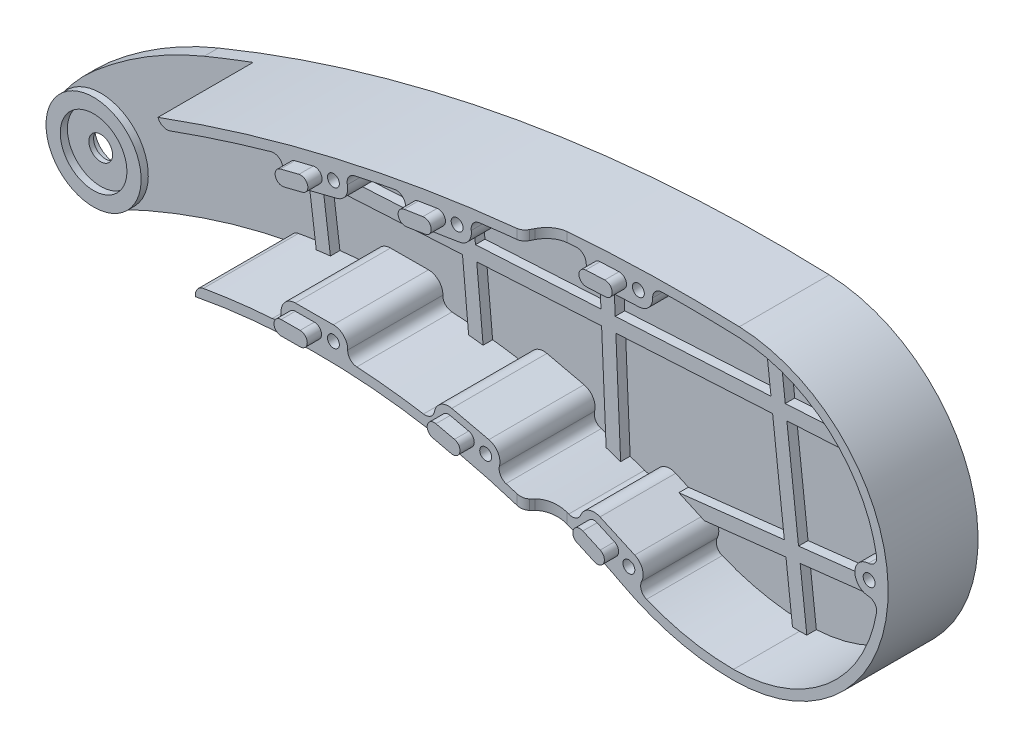
SolidWorks part; units mm, degrees
material "6061-T6 (SS)"
ref_plane "前视基准面" through (0, 0, 0) normal (0, 0, 1) x (1, 0, 0)
ref_plane "上视基准面" through (0, 0, 0) normal (0, 1, 0) x (1, 0, 0)
ref_plane "右视基准面" through (0, 0, 0) normal (1, 0, 0) x (0, 0, -1)
other "Configuration Table"
sketch "草图1" plane through (0, 0, 0) normal (0, 0, 1) x (1, 0, 0)
  line L0 (-74.3846, 0) -> (17.4339, 0) construction
  line L1 (0, 31.8895) -> (0, -25.7876) construction
  line L2 (0, 0) -> (19.2142, 13.9599) construction
  line L3 (0, 0) -> (13.9599, 19.2142) construction
  line L4 (0, 0) -> (-148.9161, -18) construction
  line L6 (0, 0) -> (-1.2281, 22.9672) construction
  line L8 (-1.2281, 22.9672) -> (-150.1441, 4.9672) construction
  line L9 (-150.1441, 4.9672) -> (-148.9161, -18) construction
  line L10 (-148.9161, -18) -> (-97.5528, -158.9319)
  line L12 (0, 0) -> (-103.1063, -167.9797) construction
  circle A117 centre (0, 0) radius 23.75 construction
  circle A118 centre (19.2142, 13.9599) radius 1.6
  circle A119 centre (13.9599, 19.2142) radius 1.6
  circle A120 centre (19.2142, -13.9599) radius 1.6
  circle A121 centre (13.9599, -19.2142) radius 1.6
  circle A122 centre (-13.9599, -19.2142) radius 1.6
  circle A123 centre (-19.2142, -13.9599) radius 1.6
  circle A124 centre (-19.2142, 13.9599) radius 1.6
  circle A125 centre (-13.9599, 19.2142) radius 1.6
  arc A126 (0, -32.5) -> (1.2171, 32.4772) centre (0, 0) ccw
  arc A127 (-157.1671, -12.3502) -> (-144.5702, -27.0063) centre (-148.9161, -18) ccw
  arc A134 (-28.3708, -24.2609) -> (-127.3793, -19.9637) centre (-83.3912, -149.2082) ccw
  arc A135 (-127.3793, -19.9637) -> (-144.5702, -27.0063) centre (-78.0965, -164.7651) ccw
  arc A136 (1.2171, 32.4772) -> (-127.1723, 9.5805) centre (-10.2849, -274.4361) ccw
  arc A138 (-23.6381, -26.5665) -> (-28.3708, -24.2609) centre (-55.9067, -86.7929) ccw
  arc A139 (0, -32.5) -> (-23.6381, -26.5665) centre (0, 17.5518) cw
  circle A153 centre (0, 0) radius 21.8
  arc A155 (-127.1723, 9.5805) -> (-150.1438, -4.5112) centre (-94.9478, -68.7195) ccw
  arc A156 (-150.1438, -4.5112) -> (-157.1671, -12.3502) centre (-123.7132, -35.2574) ccw
  point P27 (0, 0)
  point P73 (0, 0)
  point P83 (0, 0)
  point P105 (0, 0)
  dimension "D3" = 36
  dimension "D4" = 3.2
  dimension "D2" = 47.5
  dimension "D6" = 3.2
  dimension "D8" = 65
  dimension "D15" = 20
  dimension "D16" = 21.8
  dimension "D5" = 18
  dimension "D9" = 18
  dimension "D10" = 150
  dimension "D11" = 23
  dimension "D12" = 150
  dimension "D13" = 103.132
  dimension "D14" = 51.566
  dimension "D7" = 4
extrude "凸台-拉伸1" add sketch "草图1" along normal blind 3 contours A135 A134 A138 A126 A127 A125 A124 A123 A122 A121 A120 A119 A118 region at (-60.0806, 1.6127, 0)
sketch "草图2" plane through (0, 0, 0) normal (0, 0, -1) x (-1, 0, 0)
  line L0 (-28.5, 0) -> (0, 0) construction
  line L2 (0, 0) -> (-20.7479, 9.926) construction
  line L3 (-20.7479, 9.926) -> (128.1682, -8.074) construction
  line L4 (128.1682, -8.074) -> (148.9161, -18) construction
  line L5 (148.9161, -18) -> (265.6411, -112.2087) construction
  line L7 (-13.9568, 11.6234) -> (123.0533, -4.9375) construction
  line L9 (-14.5568, 6.6595) -> (122.4533, -9.9014) construction
  line L11 (19.8643, 25.54) -> (27.8561, 25.1781)
  line L13 (20.7667, -20.0677) -> (28.0595, -16.779)
  line L16 (53.5282, 22.5613) -> (61.4287, 21.3032)
  line L17 (79.2716, 17.6568) -> (87.0322, 15.7143)
  line L19 (80.013, -5.7241) -> (88.0129, -5.7588)
  line L20 (47.3274, -10.2892) -> (55.1237, -8.4956)
  line L21 (0, 0) -> (148.9161, -18) construction
  arc A111 (-1.1422, 30.4786) -> (-30.0624, 5.1483) centre (0, 0) ccw
  arc A112 (0, -30.5) -> (18.2871, -26.8842) centre (0, 17.5518) ccw
  arc A114 (75.0886, -10.9322) -> (61.0732, -12.4928) centre (83.3912, -149.2082) ccw
  arc A116 (144.5702, -27.0063) -> (157.1671, -12.3502) centre (148.9161, -18) ccw
  arc A118 (157.1671, -12.3502) -> (150.1438, -4.5112) centre (123.7132, -35.2574) ccw
  arc A119 (127.1723, 9.5805) -> (-1.2171, 32.4772) centre (10.2849, -274.4361) ccw
  arc A120 (-1.2171, 32.4772) -> (0, -32.5) centre (0, 0) ccw
  arc A121 (-1.0673, 28.48) -> (0, -28.5) centre (0, 0) ccw construction
  arc A122 (0, -32.5) -> (23.6381, -26.5665) centre (0, 17.5518) ccw
  arc A123 (28.3708, -24.2609) -> (23.6381, -26.5665) centre (55.9067, -86.7929) ccw
  arc A124 (127.3793, -19.9637) -> (28.3708, -24.2609) centre (83.3912, -149.2082) ccw
  arc A125 (144.5702, -27.0063) -> (127.3793, -19.9637) centre (78.0965, -164.7651) ccw
  arc A126 (144.5702, -27.0063) -> (157.1671, -12.3502) centre (148.9161, -18) ccw
  arc A128 (127.1723, 9.5805) -> (-1.2171, 32.4772) centre (10.2849, -274.4361) ccw
  arc A129 (-1.2171, 32.4772) -> (0, -32.5) centre (0, 0) ccw
  arc A130 (0, -32.5) -> (23.6381, -26.5665) centre (0, 17.5518) ccw
  arc A131 (28.3708, -24.2609) -> (23.6381, -26.5665) centre (55.9067, -86.7929) ccw
  arc A132 (127.3793, -19.9637) -> (28.3708, -24.2609) centre (83.3912, -149.2082) ccw
  arc A133 (144.5702, -27.0063) -> (127.3793, -19.9637) centre (78.0965, -164.7651) ccw
  arc A134 (0, -28.5) -> (21.749, -23.0407) centre (0, 17.5518) ccw construction
  arc A135 (26.7587, -20.6001) -> (21.749, -23.0407) centre (55.9067, -86.7929) ccw construction
  arc A136 (128.6681, -16.177) -> (26.7587, -20.6001) centre (83.3912, -149.2082) ccw construction
  arc A137 (146.3086, -23.4038) -> (128.6681, -16.177) centre (78.0965, -164.7651) ccw construction
  arc A138 (146.3086, -23.4038) -> (153.7238, -14.4104) centre (148.9161, -18) ccw construction
  arc A139 (153.7238, -14.4104) -> (126.0955, 5.6977) centre (120.8678, -30.5198) ccw construction
  arc A140 (126.0955, 5.6977) -> (-1.0673, 28.48) centre (10.2849, -274.4361) ccw construction
  arc A141 (-28.3421, -2.9958) -> (-28.3421, 2.9958) centre (-28.5, 0) ccw
  arc A142 (-28.3421, 2.9958) -> (-30.0624, 5.1483) centre (-28.2451, 4.837) cw
  arc A143 (-28.3421, -2.9958) -> (-30.0624, -5.1483) centre (-28.2451, -4.837) ccw
  arc A144 (-30.0624, -5.1483) -> (0, -30.5) centre (0, 0) ccw
  circle A145 centre (-28.5, 0) radius 1.6
  arc A146 (-1.1422, 30.4786) -> (0, -30.5) centre (0, 0) ccw construction
  circle A147 centre (-20.7479, 9.926) radius 7 construction
  circle A148 centre (128.1682, -8.074) radius 6 construction
  arc A149 (17.0011, 28.6182) -> (19.8643, 25.54) centre (20, 28.5369) ccw
  arc A150 (27.8561, 25.1781) -> (30.9858, 27.985) centre (27.9918, 28.175) ccw
  arc A151 (17.0011, 28.6182) -> (15.0491, 30.6555) centre (15.0181, 28.672) ccw
  arc A152 (30.9858, 27.985) -> (33.1139, 29.8374) centre (32.9655, 27.8593) cw
  arc A153 (15.0491, 30.6555) -> (-1.1422, 30.4786) centre (10.2849, -274.4361) ccw
  circle A154 centre (20, 28.5369) radius 1.6
  arc A155 (126.6313, 7.6402) -> (-1.1422, 30.4786) centre (10.2849, -274.4361) ccw construction
  arc A156 (19.3156, -24.1418) -> (20.7667, -20.0677) centre (22, -22.8025) cw
  arc A157 (28.0595, -16.779) -> (32.0817, -18.4083) centre (29.2928, -19.5138) cw
  circle A158 centre (22, -22.8025) radius 1.6
  arc A159 (19.3156, -24.1418) -> (18.2871, -26.8842) centre (17.5259, -25.0347) cw
  arc A160 (32.0817, -18.4083) -> (34.6447, -19.5434) centre (33.9409, -17.6713) ccw
  circle A161 centre (54, 25.524) radius 1.6
  arc A162 (27.5648, -22.4305) -> (22.6935, -24.8036) centre (55.9067, -86.7929) ccw construction
  arc A163 (0, -30.5) -> (22.6935, -24.8036) centre (0, 17.5518) ccw construction
  arc A164 (128.0237, -18.0703) -> (27.5648, -22.4305) centre (83.3912, -149.2082) ccw construction
  arc A165 (51.0293, 25.9419) -> (53.5282, 22.5613) centre (54, 25.524) ccw
  arc A166 (61.4287, 21.3032) -> (64.8541, 23.7404) centre (61.9005, 24.2659) ccw
  arc A167 (51.0293, 25.9419) -> (49.3187, 28.1856) centre (49.0649, 26.2183) ccw
  arc A168 (64.8541, 23.7404) -> (67.177, 25.3419) centre (66.8071, 23.393) cw
  arc A169 (49.3187, 28.1856) -> (33.1139, 29.8374) centre (10.2849, -274.4361) ccw
  circle A170 centre (80, 20.567) radius 1.6
  arc A171 (77.077, 21.2425) -> (79.2716, 17.6568) centre (80, 20.567) ccw
  arc A172 (87.0322, 15.7143) -> (90.6571, 17.8435) centre (87.7606, 18.6246) ccw
  arc A173 (77.077, 21.2425) -> (75.5687, 23.6269) centre (75.1443, 21.6892) ccw
  arc A175 (75.5687, 23.6269) -> (67.177, 25.3419) centre (10.2849, -274.4361) ccw
  circle A176 centre (48, -13.2128) radius 1.6
  circle A177 centre (80, -8.7241) radius 1.6
  arc A178 (45.1049, -13.9993) -> (47.3274, -10.2892) centre (48, -13.2128) cw
  arc A180 (45.1049, -13.9993) -> (43.7228, -16.4844) centre (43.1397, -14.5332) cw
  arc A182 (43.7228, -16.4844) -> (34.6447, -19.5434) centre (83.3912, -149.2082) ccw
  arc A183 (77.0018, -8.8285) -> (80.013, -5.7241) centre (80, -8.7241) cw
  arc A184 (88.0129, -5.7588) -> (90.9961, -8.9104) centre (87.9999, -8.7587) cw
  arc A185 (77.0018, -8.8285) -> (75.0886, -10.9322) centre (74.9666, -8.8993) cw
  arc A186 (90.9961, -8.9104) -> (92.8569, -11.0069) centre (92.9935, -9.0116) ccw
  arc A187 (107.3459, -12.77) -> (108.9673, -15.1002) centre (107, -14.7399) cw
  arc A188 (145.4394, -25.205) -> (128.0237, -18.0703) centre (78.0965, -164.7651) ccw construction
  arc A189 (128.0237, -18.0703) -> (27.5648, -22.4305) centre (83.3912, -149.2082) ccw
  arc A190 (145.4394, -25.205) -> (155.4422, -13.3729) centre (148.9161, -18) ccw construction
  arc A191 (75.5687, 23.6269) -> (93.1109, 19.2362) centre (10.2849, -274.4361) cw construction
  arc A192 (90.6571, 17.8435) -> (93.1109, 19.2362) centre (92.5724, 17.327) cw
  arc A193 (155.4422, -13.3729) -> (126.6313, 7.6402) centre (120.8678, -30.5198) ccw construction
  arc A194 (15.0491, 30.6555) -> (33.1139, 29.8374) centre (10.2849, -274.4361) cw construction
  arc A195 (49.3187, 28.1856) -> (67.177, 25.3419) centre (10.2849, -274.4361) cw construction
  arc A196 (93.1109, 19.2362) -> (114.3181, 12.4099) centre (10.2849, -274.4361) cw
  arc A197 (114.3181, 12.4099) -> (116.8779, 13.6021) centre (115, 14.2901) ccw
  arc A198 (55.1237, -8.4956) -> (58.7441, -10.8615) centre (55.7963, -11.4192) cw
  arc A199 (58.7441, -10.8615) -> (61.0732, -12.4928) centre (60.745, -10.4829) ccw
  arc A201 (27.5648, -22.4305) -> (22.6935, -24.8036) centre (55.9067, -86.7929) ccw
  arc A202 (0, -30.5) -> (22.6935, -24.8036) centre (0, 17.5518) ccw
  arc A203 (-1.1422, 30.4786) -> (0, -30.5) centre (0, 0) ccw
  arc A204 (126.4111, 7.731) -> (-1.1422, 30.4786) centre (10.2849, -274.4361) ccw
  arc A205 (148.8401, -6.0279) -> (126.4111, 7.731) centre (94.9478, -68.7195) ccw
  arc A206 (155.5169, -13.4802) -> (148.8401, -6.0279) centre (123.7132, -35.2574) ccw
  arc A207 (157.1671, -12.3502) -> (127.1723, 9.5805) centre (120.8678, -30.5198) ccw construction
  arc A208 (157.1671, -12.3502) -> (150.1438, -4.5112) centre (123.7132, -35.2574) ccw
  arc A209 (150.1438, -4.5112) -> (127.1723, 9.5805) centre (94.9478, -68.7195) ccw
  arc A210 (150.1438, -4.5112) -> (127.1723, 9.5805) centre (94.9478, -68.7195) ccw
  arc A211 (145.4394, -25.205) -> (155.5169, -13.4802) centre (148.9161, -18) ccw
  arc A212 (145.4394, -25.205) -> (128.0237, -18.0703) centre (78.0965, -164.7651) ccw
  point P113 (16.5105, -418.9921)
  arc M20 (127.1723, 9.5805) -> (-1.2171, 32.4772) centre (10.2849, -274.4361) ccw
  arc M21 (-1.2171, 32.4772) -> (0, -32.5) centre (0, 0) ccw
  arc M22 (0, -32.5) -> (23.6381, -26.5665) centre (0, 17.5518) ccw
  arc M23 (23.6381, -26.5665) -> (28.3708, -24.2609) centre (55.9067, -86.7929) cw
  arc M24 (28.3708, -24.2609) -> (127.3793, -19.9637) centre (83.3912, -149.2082) cw
  arc M25 (127.3793, -19.9637) -> (144.5702, -27.0063) centre (78.0965, -164.7651) cw
  dimension "D7" = 150
  dimension "D9" = 14
  dimension "D11" = 12
  dimension "D12" = 150
  dimension "D13" = 8
  dimension "D10" = 2.5
  dimension "D8" = 166.66
  dimension "D14" = 20
  dimension "D15" = 8
  dimension "D16" = 8
  dimension "D17" = 8
  dimension "D18" = 54
  dimension "D19" = 80
  dimension "D20" = 8
  dimension "D21" = 48
  dimension "D22" = 80
  dimension "D23" = 8
  dimension "D6" = 23
  dimension "D25" = 107
  dimension "D26" = 2
  dimension "D27" = 115
  dimension "D28" = 22
  dimension "D4" = 6
  dimension "D5" = 3.2
  dimension "D24" = 2
  dimension "D29" = 2
  dimension "D30" = 2
  dimension "D1" = 0
  dimension "D2" = 2
  dimension "D3" = 2
extrude "凸台-拉伸2" add sketch "草图2" along normal blind 20 contours M20 M21 M22 M23 M24 M25 | A152 A204 A151 A149 L11 A150 A154 | A168 A204 A167 A165 L16 A166 A161 | A192 A204 A173 A171 L17 A172 A170 | A189 A186 A184 L19 A183 A185 A177 | A199 A198 L20 A178 A180 A189 A176 | A159 A202 A201 A189 A160 A157 L13 A156 A158 | A142 A203 A143 A141 A145 region at (-24.5149, 27.9422, 0) region at (-6.9345, 32.3042, 0) region at (-58.4194, 24.4254, 0) region at (29.7748, 3.6145, 0) region at (-84.3067, 19.0872, 0) region at (-25.9289, -20.6304, 0) region at (-52.3362, -11.8146, 0) region at (-84.5374, -8.3524, 0)
sketch "草图4" plane through (0, 0, -20) normal (0, 0, -1) x (-1, 0, 0)
  line L0 (20, 28.5369) -> (27.9918, 28.175) construction
  line L3 (61.9005, 24.2659) -> (54, 25.524) construction
  line L8 (80, 20.567) -> (87.7606, 18.6246) construction
  line L9 (22, -22.8025) -> (29.2928, -19.5138) construction
  line L10 (48, -13.2128) -> (55.7963, -11.4192) construction
  line L11 (80, -8.7241) -> (87.9999, -8.7587) construction
  line L12 (29.2928, -19.5138) -> (25.6464, -21.1581) construction
  line L15 (29.9094, -20.8812) -> (26.263, -22.5255)
  line L24 (28.6761, -18.1464) -> (25.0297, -19.7907)
  line L27 (27.9918, 28.175) -> (23.9959, 28.356) construction
  line L30 (27.924, 26.6766) -> (23.9281, 26.8575)
  line L33 (28.0597, 29.6735) -> (24.0638, 29.8545)
  line L36 (61.9005, 24.2659) -> (57.9502, 24.8949) construction
  line L39 (87.7606, 18.6246) -> (83.8803, 19.5958) construction
  line L40 (87.3964, 17.1695) -> (83.5161, 18.1407)
  line L41 (88.1248, 20.0797) -> (84.2445, 21.0509)
  line L42 (87.9999, -8.7587) -> (84, -8.7414) construction
  line L43 (87.9934, -10.2587) -> (83.9935, -10.2414)
  line L44 (88.0064, -7.2587) -> (84.0065, -7.2414)
  line L45 (55.7963, -11.4192) -> (51.8982, -12.316) construction
  line L46 (56.1326, -12.881) -> (52.2345, -13.7778)
  line L47 (55.46, -9.9574) -> (51.5619, -10.8542)
  line L48 (61.6646, 22.7845) -> (57.7143, 23.4136)
  line L49 (62.1363, 25.7472) -> (58.1861, 26.3763)
  arc A24 (29.9094, -20.8812) -> (28.6761, -18.1464) centre (29.2928, -19.5138) ccw
  arc A25 (25.0297, -19.7907) -> (26.263, -22.5255) centre (25.6464, -21.1581) ccw
  arc A26 (27.924, 26.6766) -> (28.0597, 29.6735) centre (27.9918, 28.175) ccw
  arc A27 (24.0638, 29.8545) -> (23.9281, 26.8575) centre (23.9959, 28.356) ccw
  arc A30 (87.3964, 17.1695) -> (88.1248, 20.0797) centre (87.7606, 18.6246) ccw
  arc A31 (84.2445, 21.0509) -> (83.5161, 18.1407) centre (83.8803, 19.5958) ccw
  arc A32 (87.9934, -10.2587) -> (88.0064, -7.2587) centre (87.9999, -8.7587) ccw
  arc A33 (84.0065, -7.2414) -> (83.9935, -10.2414) centre (84, -8.7414) ccw
  arc A34 (56.1326, -12.881) -> (55.46, -9.9574) centre (55.7963, -11.4192) ccw
  arc A35 (51.5619, -10.8542) -> (52.2345, -13.7778) centre (51.8982, -12.316) ccw
  arc A36 (61.6646, 22.7845) -> (62.1363, 25.7472) centre (61.9005, 24.2659) ccw
  arc A37 (58.1861, 26.3763) -> (57.7143, 23.4136) centre (57.9502, 24.8949) ccw
  point P12 (27.4696, -20.3359)
  point P18 (25.9939, 28.2655)
  point P24 (59.9253, 24.5804)
  point P30 (85.8204, 19.1102)
  point P36 (85.9999, -8.7501)
  point P42 (53.8473, -11.8676)
  dimension "D2" = 1.5
  dimension "D1" = 4
extrude "凸台-拉伸3" add sketch "草图4" along normal blind 3 contours L44 A33 L43 A32 | L33 A27 L30 A26 | L49 A37 L48 A36 | A30 L41 A31 L40 | A34 L47 A35 L46 | A24 L24 A25 L15 region at (-85.9999, -8.7501, -20)
sketch "草图5" plane through (0, 0, -20) normal (0, 0, -1) x (-1, 0, 0)
  circle A0 centre (80, -8.7241) radius 1.6 construction
  circle A2 centre (-28.5, 0) radius 1.6 construction
  circle A4 centre (-28.5, 0) radius 1.6
  circle A6 centre (54, 25.524) radius 1.6 construction
  circle A8 centre (80, 20.567) radius 1.6 construction
  circle A10 centre (80, -8.7241) radius 1.6
  circle A12 centre (48, -13.2128) radius 1.6 construction
  circle A14 centre (22, -22.8025) radius 1.6 construction
  circle A27 centre (20, 28.5369) radius 1.6 construction
  circle A28 centre (54, 25.524) radius 1.6
  circle A29 centre (80, 20.567) radius 1.6
  circle A31 centre (48, -13.2128) radius 1.6
  circle A32 centre (22, -22.8025) radius 1.6
  circle A33 centre (20, 28.5369) radius 1.6
extrude "切除-拉伸1" cut sketch "草图5" against normal up to next
sketch "草图10" plane through (0, 0, 0) normal (0, 0, -1) x (-1, 0, 0)
  circle A0 centre (148.9161, -18) radius 2.5
  dimension "D1" = 5
extrude "切除-拉伸4" cut sketch "草图10" against normal up to next
sketch "草图11" plane through (0, 0, 3) normal (0, 0, 1) x (1, 0, 0)
  circle A0 centre (-148.9161, -18) radius 4.25
  dimension "D1" = 8.5
extrude "切除-拉伸5" cut sketch "草图11" against normal blind 2
sketch "草图13" plane through (0, 0, 3) normal (0, 0, 1) x (1, 0, 0)
  line L0 (-82.9126, 19.8482) -> (-83.8746, 23.7461)
  line L1 (-77.0737, 21.2281) -> (-77.9584, 25.1442)
  line L2 (-56.9642, 25.062) -> (-57.5825, 29.0289)
  line L3 (-51.0272, 25.9272) -> (-51.5669, 29.9056)
  line L4 (-22.9974, 28.4111) -> (-23.1657, 32.4224)
  line L5 (-17.0007, 28.6034) -> (-17.0897, 32.6173)
  line L6 (-83, -8.7157) -> (-83.011, -12.6837)
  line L7 (-77.0031, -8.8605) -> (-77.1835, -12.8243)
  line L10 (-24.5347, -21.1976) -> (-26.898, -24.9303)
  line L11 (-19.2779, -24.0635) -> (-21.0383, -27.8637)
  line L12 (28.5, 3) -> (32.3612, 3)
  line L13 (28.5, -3) -> (32.3612, -3)
  line L14 (28.5, 3) -> (28.5, -3) construction
  line L16 (-45.1135, -14.0301) -> (-46.1946, -17.848)
  line L17 (-50.9188, -12.5194) -> (-51.8359, -16.3799)
  arc A0 (-82.9126, 19.8482) -> (-77.0737, 21.2281) centre (-80, 20.567) ccw
  arc A1 (-56.9642, 25.062) -> (-51.0272, 25.9272) centre (-54, 25.524) ccw
  arc A2 (-22.9974, 28.4111) -> (-17.0007, 28.6034) centre (-20, 28.5369) ccw
  arc A3 (28.5, 3) -> (28.5, -3) centre (28.5, 0) ccw
  arc A5 (-45.1135, -14.0301) -> (-50.9676, -12.7729) centre (-48, -13.2128) ccw
  arc A7 (-23.6381, -26.5665) -> (0, -32.5) centre (0, 17.5518) ccw construction
  arc A8 (1.2171, 32.4772) -> (-127.1723, 9.5805) centre (-10.2849, -274.4361) ccw construction
  arc A9 (-28.3708, -24.2609) -> (-127.3793, -19.9637) centre (-83.3912, -149.2082) ccw construction
  arc A11 (-23.6381, -26.5665) -> (-28.3708, -24.2609) centre (-55.9067, -86.7929) ccw construction
  arc A12 (0, -32.5) -> (1.2171, 32.4772) centre (0, 0) ccw construction
  arc A13 (-17.0897, 32.6173) -> (-23.1657, 32.4224) centre (-10.2849, -274.4361) ccw
  arc A15 (32.3612, -3) -> (32.3612, 3) centre (0, 0) ccw
  arc A16 (-77.1835, -12.8243) -> (-83.011, -12.6837) centre (-83.3912, -149.2082) ccw
  arc A18 (-19.2779, -24.0635) -> (-24.5347, -21.1976) centre (-22, -22.8025) ccw
  arc A19 (-46.1946, -17.848) -> (-51.8359, -16.3799) centre (-83.3912, -149.2082) ccw
  arc A20 (-77.0031, -8.8605) -> (-83, -8.7157) centre (-80, -8.7241) ccw
  arc A21 (-77.9584, 25.1442) -> (-83.8746, 23.7461) centre (-10.2849, -274.4361) ccw
  arc A22 (-51.5669, 29.9056) -> (-57.5825, 29.0289) centre (-10.2849, -274.4361) ccw
  arc A23 (-23.6381, -26.5665) -> (-21.0383, -27.8637) centre (0, 17.5518) ccw
  arc A24 (-23.6381, -26.5665) -> (-26.898, -24.9303) centre (-55.9067, -86.7929) ccw
  circle M9 centre (28.5, 0) radius 1.6
  circle M10 centre (-54, 25.524) radius 1.6
  circle M11 centre (-80, 20.567) radius 1.6
  circle M12 centre (-80, -8.7241) radius 1.6
  circle M13 centre (-48, -13.2128) radius 1.6
  circle M14 centre (-22, -22.8025) radius 1.6
  circle M15 centre (-20, 28.5369) radius 1.6
  arc M17 (-127.3793, -19.9637) -> (-28.3708, -24.2609) centre (-83.3912, -149.2082) cw
  arc M19 (-23.6381, -26.5665) -> (0, -32.5) centre (0, 17.5518) ccw
  arc M20 (0, -32.5) -> (1.2171, 32.4772) centre (0, 0) ccw
  arc M21 (1.2171, 32.4772) -> (-127.1723, 9.5805) centre (-10.2849, -274.4361) ccw
  dimension "D1" = 6
  dimension "D2" = 6
  dimension "D3" = 3
  dimension "D4" = 6
  dimension "D5" = 0
extrude "切除-拉伸6" cut sketch "草图13" against normal blind 2 contours A5 M17 M13 | L11 A18 L10 M19 M14 | L12 L14 L13 M9 M20 | L14 A3 M9 | L4 A2 L5 M21 M15 | L2 A1 L3 M21 M10 | L0 A0 L1 M21 M11 | L7 A20 L6 M17 M12 region at (-22.2972, -27.133, 3) region at (30.7421, 0, 3) region at (-20.1252, 32.441, 3) region at (-54.5626, 29.3843, 3) region at (-83.2943, 21.8217, 3) region at (28.4329, 2.3, 3) region at (-79.9298, -5.8179, 3) region at (-51.2776, -14.4733, 3)
sketch "草图14" plane through (0, 0, 0) normal (0, 0, -1) x (-1, 0, 0)
  circle A0 centre (148.9161, -18) radius 10
  circle A1 centre (148.9161, -18) radius 7
  dimension "D1" = 14
  dimension "D2" = 20
extrude "凸台-拉伸4" add sketch "草图14" along normal blind 1.5
sketch "草图16" plane through (0, 0, 0) normal (0, 0, -1) x (-1, 0, 0)
  line L2 (69.9, 24.8123) -> (66.5383, -11.7121)
  line L3 (72.857, 24.208) -> (69.5822, -11.3731)
  line L4 (41.2273, 29.1197) -> (39.1573, -17.9354) construction
  line L5 (68.061, -11.534) -> (71.3789, 24.5139) construction
  line L6 (39.7324, 29.2684) -> (37.6328, -18.459)
  line L7 (42.7219, 28.9636) -> (40.6809, -17.4318)
  line L8 (103.7768, 16.0167) -> (100.1246, -11.6975) construction
  line L9 (102.3249, 16.48) -> (98.6344, -11.5244)
  line L10 (105.2277, 15.5457) -> (101.6126, -11.8868)
  arc A0 (69.5822, -11.3731) -> (66.5383, -11.7121) centre (83.3912, -149.2082) ccw
  arc A1 (72.857, 24.208) -> (69.9, 24.8123) centre (10.2849, -274.4361) ccw
  arc A2 (43.7228, -16.4844) -> (34.6447, -19.5434) centre (83.3912, -149.2082) ccw construction
  arc A5 (49.3187, 28.1856) -> (33.1139, 29.8374) centre (10.2849, -274.4361) ccw construction
  arc A8 (75.5687, 23.6269) -> (67.177, 25.3419) centre (10.2849, -274.4361) ccw construction
  arc A9 (75.0886, -10.9322) -> (61.0732, -12.4928) centre (83.3912, -149.2082) ccw construction
  arc A10 (75.0886, -10.9322) -> (61.0732, -12.4928) centre (83.3912, -149.2082) ccw construction
  arc A11 (49.3187, 28.1856) -> (33.1139, 29.8374) centre (10.2849, -274.4361) ccw construction
  arc A12 (43.7228, -16.4844) -> (34.6447, -19.5434) centre (83.3912, -149.2082) ccw construction
  arc A13 (40.6809, -17.4318) -> (37.6328, -18.459) centre (83.3912, -149.2082) ccw
  arc A14 (42.7219, 28.9636) -> (39.7324, 29.2684) centre (10.2849, -274.4361) ccw
  arc A15 (114.3181, 12.4099) -> (93.1109, 19.2362) centre (10.2849, -274.4361) ccw construction
  arc A16 (107.3459, -12.77) -> (92.8569, -11.0069) centre (83.3912, -149.2082) ccw construction
  arc A17 (101.6126, -11.8868) -> (98.6344, -11.5244) centre (83.3912, -149.2082) ccw
  arc A18 (105.2277, 15.5457) -> (102.3249, 16.48) centre (10.2849, -274.4361) ccw
  point P33 (71.3789, 24.5139)
  dimension "D3" = 3
  dimension "D1" = 3
  dimension "D2" = 3
extrude "凸台-拉伸5" add sketch "草图16" along normal blind 2
sketch "草图17" plane through (0, 0, 0) normal (0, 0, -1) x (-1, 0, 0)
  line L0 (41.7014, 5.7659) -> (100.4797, 2.4778) construction
  line L1 (40.6809, -17.4318) -> (42.7219, 28.9636) construction
  line L2 (102.3249, 16.48) -> (98.6344, -11.5244) construction
  line L3 (41.7673, 7.2646) -> (100.6762, 3.9692)
  line L4 (102.3249, 16.48) -> (98.6344, -11.5244) construction
  line L5 (41.6355, 4.2673) -> (100.2831, 0.9865)
  line L6 (100.6762, 3.9692) -> (100.2831, 0.9865)
  line L7 (41.6355, 4.2673) -> (41.7673, 7.2646)
  dimension "D1" = 3
extrude "凸台-拉伸6" add sketch "草图17" along normal blind 2
fillet "圆角1" radius 2 14 edges at (-83.8746, 23.7461, 2) (-77.9584, 25.1442, 2) (-57.5825, 29.0289, 2) (-51.5669, 29.9056, 2) (-77.1835, -12.8243, 2) (-83.011, -12.6837, 2) (-21.0383, -27.8637, 2) (32.3612, 3, 2) (32.3612, -3, 2) (-23.1657, 32.4224, 2) (-17.0897, 32.6173, 2) (-46.1946, -17.848, 2) (-51.8359, -16.3799, 2) (-26.898, -24.9303, 2)
sketch "草图20" plane through (0, 0, 3) normal (0, 0, 1) x (1, 0, 0)
  line L0 (30.0874, 3) -> (28.5, 3) construction
  line L1 (28.5, -3) -> (30.0874, -3) construction
  line L2 (-20.1802, -26.0112) -> (-19.2779, -24.0635) construction
  line L3 (-24.5347, -21.1976) -> (-25.967, -23.4599) construction
  line L4 (-45.6536, -15.9376) -> (-45.1135, -14.0301) construction
  line L5 (-50.9188, -12.5194) -> (-51.377, -14.4481) construction
  line L6 (-77.0932, -10.8408) -> (-77.0031, -8.8605) construction
  line L7 (-83, -8.7157) -> (-83.0055, -10.6981) construction
  line L8 (-23.0816, 30.4176) -> (-22.9974, 28.4111) construction
  line L9 (-17.0007, 28.6034) -> (-17.0452, 30.6112) construction
  line L10 (-57.2735, 27.0463) -> (-56.9642, 25.062) construction
  line L11 (-51.0272, 25.9272) -> (-51.2972, 27.9173) construction
  line L12 (-83.3938, 21.798) -> (-82.9126, 19.8482) construction
  line L13 (-77.0737, 21.2281) -> (-77.5162, 23.187) construction
  line L14 (30.0874, 3) -> (28.5, 3)
  line L15 (28.5, -3) -> (30.0874, -3)
  line L16 (-20.1802, -26.0112) -> (-19.2779, -24.0635)
  line L17 (-24.5347, -21.1976) -> (-25.967, -23.4599)
  line L18 (-45.6536, -15.9376) -> (-45.1135, -14.0301)
  line L19 (-50.9188, -12.5194) -> (-51.377, -14.4481)
  line L20 (-77.0932, -10.8408) -> (-77.0031, -8.8605)
  line L21 (-83, -8.7157) -> (-83.0055, -10.6981)
  line L22 (-23.0816, 30.4176) -> (-22.9974, 28.4111)
  line L23 (-17.0007, 28.6034) -> (-17.0452, 30.6112)
  line L24 (-57.2735, 27.0463) -> (-56.9642, 25.062)
  line L25 (-51.0272, 25.9272) -> (-51.2972, 27.9173)
  line L26 (-83.3938, 21.798) -> (-82.9126, 19.8482)
  line L27 (-77.0737, 21.2281) -> (-77.5162, 23.187)
  arc A0 (28.5, 3) -> (28.5, -3) centre (28.5, 0) ccw construction
  arc A1 (32.0603, -5.3279) -> (30.0874, -3) centre (30.0874, -5) ccw construction
  arc A2 (32.0603, -5.3279) -> (32.0603, 5.3279) centre (0, 0) ccw construction
  arc A3 (30.0874, 3) -> (32.0603, 5.3279) centre (30.0874, 5) ccw construction
  arc A4 (-19.2779, -24.0635) -> (-24.5347, -21.1976) centre (-22, -22.8025) ccw construction
  arc A5 (-28.4615, -24.221) -> (-25.967, -23.4599) centre (-27.6568, -22.39) ccw construction
  arc A7 (-23.6381, -26.5665) -> (-19.1298, -28.7) centre (0, 17.5518) ccw construction
  arc A8 (-20.1802, -26.0112) -> (-19.1298, -28.7) centre (-18.3654, -26.8519) ccw construction
  arc A9 (-45.1135, -14.0301) -> (-50.9188, -12.5194) centre (-48, -13.2128) ccw construction
  arc A10 (-53.7569, -15.9382) -> (-51.377, -14.4481) centre (-53.3228, -13.9859) ccw construction
  arc A11 (-44.3019, -18.3987) -> (-53.7569, -15.9382) centre (-83.3912, -149.2082) ccw construction
  arc A12 (-45.6536, -15.9376) -> (-44.3019, -18.3987) centre (-43.7293, -16.4825) ccw construction
  arc A13 (-77.0031, -8.8605) -> (-83, -8.7157) centre (-80, -8.7241) ccw construction
  arc A14 (-84.9822, -12.6924) -> (-83.0055, -10.6981) centre (-85.0055, -10.6925) ccw construction
  arc A15 (-75.2151, -12.9282) -> (-84.9822, -12.6924) centre (-83.3912, -149.2082) ccw construction
  arc A16 (-77.0932, -10.8408) -> (-75.2151, -12.9282) centre (-75.0953, -10.9318) ccw construction
  arc A17 (-22.9974, 28.4111) -> (-17.0007, 28.6034) centre (-20, 28.5369) ccw construction
  arc A18 (-15.0769, 32.6553) -> (-17.0452, 30.6112) centre (-15.0457, 30.6555) ccw construction
  arc A19 (-15.0769, 32.6553) -> (-25.1768, 32.3314) centre (-10.2849, -274.4361) ccw construction
  arc A20 (-23.0816, 30.4176) -> (-25.1768, 32.3314) centre (-25.0798, 30.3338) ccw construction
  arc A21 (-56.9642, 25.062) -> (-51.0272, 25.9272) centre (-54, 25.524) ccw construction
  arc A22 (-49.5711, 30.1696) -> (-51.2972, 27.9173) centre (-49.3153, 28.1861) ccw construction
  arc A23 (-49.5711, 30.1696) -> (-59.5706, 28.7124) centre (-10.2849, -274.4361) ccw construction
  arc A24 (-57.2735, 27.0463) -> (-59.5706, 28.7124) centre (-59.2496, 26.7383) ccw construction
  arc A25 (-82.9126, 19.8482) -> (-77.0737, 21.2281) centre (-80, 20.567) ccw construction
  arc A26 (-75.9933, 25.5814) -> (-77.5162, 23.187) centre (-75.5654, 23.6277) ccw construction
  arc A27 (-75.9933, 25.5814) -> (-85.8275, 23.2574) centre (-10.2849, -274.4361) ccw construction
  arc A28 (-83.3938, 21.798) -> (-85.8275, 23.2574) centre (-85.3355, 21.3188) ccw construction
  arc A29 (28.5, 3) -> (28.5, -3) centre (28.5, 0) ccw
  arc A30 (32.0603, -5.3279) -> (30.0874, -3) centre (30.0874, -5) ccw
  arc A31 (32.0603, -5.3279) -> (32.0603, 5.3279) centre (0, 0) ccw
  arc A32 (30.0874, 3) -> (32.0603, 5.3279) centre (30.0874, 5) ccw
  arc A33 (-19.2779, -24.0635) -> (-24.5347, -21.1976) centre (-22, -22.8025) ccw
  arc A34 (-28.4615, -24.221) -> (-25.967, -23.4599) centre (-27.6568, -22.39) ccw
  arc A35 (-23.6381, -26.5665) -> (-28.4615, -24.221) centre (-55.9071, -86.7927) ccw
  arc A36 (-23.6381, -26.5665) -> (-19.1298, -28.7) centre (0, 17.5518) ccw
  arc A37 (-20.1802, -26.0112) -> (-19.1298, -28.7) centre (-18.3654, -26.8519) ccw
  arc A38 (-45.1135, -14.0301) -> (-50.9188, -12.5194) centre (-48, -13.2128) ccw
  arc A39 (-53.7569, -15.9382) -> (-51.377, -14.4481) centre (-53.3228, -13.9859) ccw
  arc A40 (-44.3019, -18.3987) -> (-53.7569, -15.9382) centre (-83.3912, -149.2082) ccw
  arc A41 (-45.6536, -15.9376) -> (-44.3019, -18.3987) centre (-43.7293, -16.4825) ccw
  arc A42 (-77.0031, -8.8605) -> (-83, -8.7157) centre (-80, -8.7241) ccw
  arc A43 (-84.9822, -12.6924) -> (-83.0055, -10.6981) centre (-85.0055, -10.6925) ccw
  arc A44 (-75.2151, -12.9282) -> (-84.9822, -12.6924) centre (-83.3912, -149.2082) ccw
  arc A45 (-77.0932, -10.8408) -> (-75.2151, -12.9282) centre (-75.0953, -10.9318) ccw
  arc A46 (-22.9974, 28.4111) -> (-17.0007, 28.6034) centre (-20, 28.5369) ccw
  arc A47 (-15.0769, 32.6553) -> (-17.0452, 30.6112) centre (-15.0457, 30.6555) ccw
  arc A48 (-15.0769, 32.6553) -> (-25.1768, 32.3314) centre (-10.2849, -274.4361) ccw
  arc A49 (-23.0816, 30.4176) -> (-25.1768, 32.3314) centre (-25.0798, 30.3338) ccw
  arc A50 (-56.9642, 25.062) -> (-51.0272, 25.9272) centre (-54, 25.524) ccw
  arc A51 (-49.5711, 30.1696) -> (-51.2972, 27.9173) centre (-49.3153, 28.1861) ccw
  arc A52 (-49.5711, 30.1696) -> (-59.5706, 28.7124) centre (-10.2849, -274.4361) ccw
  arc A53 (-57.2735, 27.0463) -> (-59.5706, 28.7124) centre (-59.2496, 26.7383) ccw
  arc A54 (-82.9126, 19.8482) -> (-77.0737, 21.2281) centre (-80, 20.567) ccw
  arc A55 (-75.9933, 25.5814) -> (-77.5162, 23.187) centre (-75.5654, 23.6277) ccw
  arc A56 (-75.9933, 25.5814) -> (-85.8275, 23.2574) centre (-10.2849, -274.4361) ccw
  arc A57 (-83.3938, 21.798) -> (-85.8275, 23.2574) centre (-85.3355, 21.3188) ccw
  circle A58 centre (-19.2142, -13.9599) radius 1.6 construction
  circle A59 centre (-13.9599, -19.2142) radius 1.6 construction
  circle A60 centre (13.9599, -19.2142) radius 1.6 construction
  circle A61 centre (19.2142, -13.9599) radius 1.6 construction
  circle A62 centre (19.2142, 13.9599) radius 1.6 construction
  circle A63 centre (13.9599, 19.2142) radius 1.6 construction
  circle A64 centre (0, 0) radius 21.8 construction
  circle A65 centre (-19.2142, 13.9599) radius 1.6 construction
  circle A66 centre (-13.9599, 19.2142) radius 1.6 construction
  circle A67 centre (-19.2142, -13.9599) radius 1.6
  circle A68 centre (-13.9599, -19.2142) radius 1.6
  circle A69 centre (13.9599, -19.2142) radius 1.6
  circle A70 centre (19.2142, -13.9599) radius 1.6
  circle A71 centre (19.2142, 13.9599) radius 1.6
  circle A72 centre (13.9599, 19.2142) radius 1.6
  circle A73 centre (0, 0) radius 21.8
  circle A74 centre (-19.2142, 13.9599) radius 1.6
  circle A75 centre (-13.9599, 19.2142) radius 1.6
extrude "凸台-拉伸7" add sketch "草图20" against normal up to surface (3 mm away) up to face at (20.8142, 13.9599, 0)
sketch "草图21" plane through (0, 0, -20) normal (0, 0, -1) x (-1, 0, 0)
  circle A0 centre (-28.5, 0) radius 1.6 construction
  circle A1 centre (22, -22.8025) radius 1.6 construction
  circle A2 centre (48, -13.2128) radius 1.6 construction
  circle A3 centre (80, -8.7241) radius 1.6 construction
  circle A4 centre (80, 20.567) radius 1.6 construction
  circle A5 centre (54, 25.524) radius 1.6 construction
  circle A6 centre (20, 28.5369) radius 1.6 construction
  circle A7 centre (-28.5, 0) radius 1.6
  circle A8 centre (22, -22.8025) radius 1.6
  circle A9 centre (48, -13.2128) radius 1.6
  circle A10 centre (80, -8.7241) radius 1.6
  circle A11 centre (80, 20.567) radius 1.6
  circle A12 centre (54, 25.524) radius 1.6
  circle A13 centre (20, 28.5369) radius 1.6
extrude "凸台-拉伸8" add sketch "草图21" against normal up to surface (20 mm away) up to face at (-18.4, 28.5369, 0)
sketch "草图25" plane through (0, 0, 0) normal (0, 0, -1) x (-1, 0, 0)
  line L0 (38.7718, 7.4321) -> (6.0287, 9.2638)
  line L1 (39.7324, 29.2684) -> (37.6328, -18.459) construction
  line L2 (38.64, 4.4348) -> (5.6894, 6.2781)
  line L3 (68.1491, 5.7888) -> (41.7673, 7.2646) construction
  line L4 (41.6355, 4.2673) -> (67.8739, 2.7995) construction
  line L5 (38.7718, 7.4321) -> (38.64, 4.4348)
  line L6 (8.4634, 30.6872) -> (6.0287, 9.2638)
  line L7 (5.4403, 30.6542) -> (3.0284, 9.4317)
  line L8 (6.9523, 30.6745) -> (0, -30.5) construction
  line L9 (5.6894, 6.2781) -> (3.2186, -15.4623)
  line L10 (3.0284, 9.4317) -> (-28.3738, 11.1883)
  line L11 (2.6891, 6.4459) -> (0.2378, -15.1236)
  line L12 (2.6891, 6.4459) -> (-29.3661, 8.2391)
  line L13 (-28.0805, -11.9053) -> (0.2378, -15.1236)
  line L14 (-26.4972, -15.1045) -> (-0.1009, -18.1044)
  line L15 (3.2186, -15.4623) -> (25.3914, -17.9822)
  line L16 (20.7667, -20.0677) -> (28.0595, -16.779) construction
  line L17 (2.8799, -18.4432) -> (20.0437, -20.3938)
  line L18 (20.7667, -20.0677) -> (28.0595, -16.779) construction
  line L19 (20.0437, -20.3938) -> (25.3914, -17.9822)
  line L20 (2.8799, -18.4432) -> (1.5124, -30.4762)
  line L21 (-0.1009, -18.1044) -> (-1.5054, -30.4628)
  arc A0 (-1.1422, 30.4786) -> (-30.0624, 5.1483) centre (0, 0) ccw construction
  arc A1 (-28.3738, 11.1883) -> (-29.3661, 8.2391) centre (0, 0) ccw
  arc A2 (15.0491, 30.6555) -> (-1.1422, 30.4786) centre (10.2849, -274.4361) ccw construction
  arc A3 (-30.0624, -5.1483) -> (0, -30.5) centre (0, 0) ccw construction
  arc A4 (15.0491, 30.6555) -> (-1.1422, 30.4786) centre (10.2849, -274.4361) ccw construction
  arc A5 (-30.0624, -5.1483) -> (0, -30.5) centre (0, 0) ccw construction
  arc A6 (8.4634, 30.6872) -> (5.4403, 30.6542) centre (10.2849, -274.4361) ccw
  arc A8 (-28.0805, -11.9053) -> (-26.4972, -15.1045) centre (0, 0) ccw
  arc A9 (-1.5054, -30.4628) -> (0, -30.5) centre (0, 0) ccw
  arc A10 (0, -30.5) -> (18.2871, -26.8842) centre (0, 17.5518) ccw construction
  arc A11 (0, -30.5) -> (1.5124, -30.4762) centre (0, 17.5518) ccw
  dimension "D4" = 30.5
  dimension "D1" = 3
  dimension "D2" = 3
  dimension "D3" = 15
extrude "凸台-拉伸9" add sketch "草图25" along normal blind 2
sketch "草图26" plane through (0, 0, 0) normal (0, 1, 0) x (1, 0, 0)
  line L0 (0, 20) -> (-41.41, 20) construction
  line L1 (32.5, 15.9) -> (-35, 15.9)
  line L2 (32.5, -3) -> (32.5, 20) construction
  line L3 (32.5, 20) -> (0, 20) construction
  line L4 (1.2171, 20) -> (-116.8779, 20) construction
  line L5 (-41.41, 20) -> (-32.2761, 20) construction
  line L6 (32.5, 15.9) -> (36.9453, 15.9)
  line L7 (36.9453, 15.9) -> (36.9453, 30.4956)
  line L8 (36.9453, 30.4956) -> (-41.41, 30.4956)
  line L9 (-41.41, 30.4956) -> (-41.41, 20)
  line L10 (-39.7153, 19.035) -> (-39.2785, 18.3127)
  arc A1 (-39.7153, 19.035) -> (-41.41, 20) centre (-41.4267, 18.0001) ccw
  arc A2 (-39.2785, 18.3127) -> (-35, 15.9) centre (-35, 20.9) ccw
  dimension "D2" = 2
  dimension "D3" = 5
  dimension "D1" = 35
  dimension "D4" = 4.1
  dimension "D5" = 6.41
extrude "切除-拉伸7" cut sketch "草图26" against normal through all both and the other way through all
sketch "草图31" plane through (0, 0, -20) normal (0, 0, -1) x (-1, 0, 0)
  point P0 (54, 25.524)
  point P1 (48, -13.2128)
  point P3 (80, -8.7241)
  point P5 (80, 20.567)
hole_wizard "M3 螺纹孔4" positions "草图31" profile "草图32" tap size "M3" standard "GB"
sketch "草图32" plane through (-54, 25.524, -20) normal (1, 0, 0) x (0, 1, 0)
  line L0 (0, 0) -> (0, 5.7511)
  line L1 (0, 5.7511) -> (1.25, 5)
  line L2 (1.25, 5) -> (1.25, 0)
  line L5 (1.25, 0) -> (0, 0)
  line L10 (0, 5.7511) -> (-1.25, 5) construction
  line L11 (0, -6.35) -> (0, 107.95) construction
  dimension "螺纹孔钻头直径" = 2.5
  dimension "螺纹孔钻头深度" = 5
  dimension "导头角度" = 118
cosmetic thread "孔螺蚊线15" parameters "D1"=6, "D2"=3
cosmetic thread "孔螺蚊线16" parameters "D1"=6, "D2"=3
cosmetic thread "孔螺蚊线17" parameters "D1"=6, "D2"=3
cosmetic thread "孔螺蚊线18" parameters "D1"=6, "D2"=3
sketch "草图33" plane through (0, 0, -15.9) normal (0, 0, -1) x (-1, 0, 0)
  point P0 (20, 28.5369)
  point P1 (22, -22.8025)
  point P3 (-28.5, 0)
hole_wizard "M3 螺纹孔5" positions "草图33" profile "草图34" tap size "M3" standard "GB"
sketch "草图34" plane through (-20, 28.5369, -15.9) normal (1, 0, 0) x (0, 1, 0)
  line L0 (0, 0) -> (0, 5.7511)
  line L1 (0, 5.7511) -> (1.25, 5)
  line L2 (1.25, 5) -> (1.25, 0)
  line L5 (1.25, 0) -> (0, 0)
  line L10 (0, 5.7511) -> (-1.25, 5) construction
  line L11 (0, -6.35) -> (0, 107.95) construction
  dimension "螺纹孔钻头直径" = 2.5
  dimension "螺纹孔钻头深度" = 5
  dimension "导头角度" = 118
cosmetic thread "孔螺蚊线19" parameters "D1"=6, "D2"=3
cosmetic thread "孔螺蚊线20" parameters "D1"=6, "D2"=3
cosmetic thread "孔螺蚊线21" parameters "D1"=6, "D2"=3
sketch "草图36" plane through (0, 0, -15.9) normal (0, 0, -1) x (-1, 0, 0)
  line L0 (20, 28.5369) -> (27.9918, 28.175) construction
  line L1 (22, -22.8025) -> (29.2928, -19.5138) construction
  line L2 (29.2928, -19.5138) -> (25.6464, -21.1581) construction
  line L3 (29.9094, -20.8812) -> (26.263, -22.5255)
  line L4 (28.6761, -18.1464) -> (25.0297, -19.7907)
  line L5 (27.9918, 28.175) -> (23.9959, 28.356) construction
  line L6 (27.924, 26.6766) -> (23.9281, 26.8575)
  line L7 (28.0597, 29.6735) -> (24.0638, 29.8545)
  arc A0 (29.9094, -20.8812) -> (28.6761, -18.1464) centre (29.2928, -19.5138) ccw
  arc A1 (25.0297, -19.7907) -> (26.263, -22.5255) centre (25.6464, -21.1581) ccw
  arc A2 (27.924, 26.6766) -> (28.0597, 29.6735) centre (27.9918, 28.175) ccw
  arc A3 (24.0638, 29.8545) -> (23.9281, 26.8575) centre (23.9959, 28.356) ccw
  point P8 (27.4696, -20.3359)
  point P14 (25.9939, 28.2655)
  dimension "D1" = 1.5
  dimension "D2" = 1.5
extrude "凸台-拉伸11" add sketch "草图36" along normal blind 3
mirror "镜向1" about plane through (0, 0, -20) normal (0, 0, -1) of bodies 163 148
delete or keep bodies "实体-删除/保留 1" type delete bodies bodies 163
ref_plane "基准面1" through (0, 0, -30) normal (0, 0, 1) x (1, 0, 0)
sketch "草图37" plane through (0, 0, -30) normal (0, 0, 1) x (1, 0, 0)
  point P0 (0, 0)
  point P1 (-148.9161, -18)
